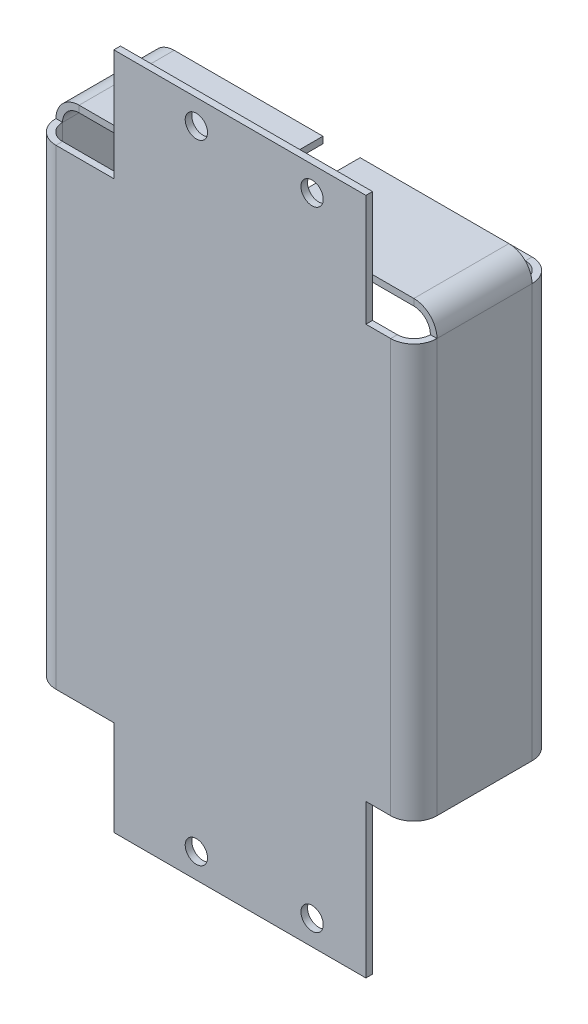
SolidWorks part; units mm, degrees
note: The reader was unsure of these and kept them because the rebuilt part matched: flange length of "Edge-Flange1", "Edge-Flange4", "Edge-Flange5".
ref_plane "Front Plane" through (0, 0, 0) normal (0, 0, 1) x (1, 0, 0)
ref_plane "Top Plane" through (0, 0, 0) normal (0, 1, 0) x (1, 0, 0)
ref_plane "Right Plane" through (0, 0, 0) normal (1, 0, 0) x (0, 0, -1)
sketch "Sketch1" plane through (0, 0, 0) normal (0, 0, 1) x (1, 0, 0)
  line L0 (16.25, 0) -> (16.25, -18.5)
  line L1 (21.25, 50) -> (16.25, 50)
  line L2 (21.25, 50) -> (21.25, 0)
  line L3 (21.25, 0) -> (16.25, 0)
  line L4 (-23.25, 50) -> (-23.25, -7)
  line L5 (16.25, -18.5) -> (-14.25, -18.5)
  line L6 (-14.25, -18.5) -> (-14.25, -7)
  line L7 (16.25, 50) -> (16.25, 63.5)
  line L9 (16.25, 63.5) -> (-14.25, 63.5)
  line L10 (-14.25, 63.5) -> (-14.25, 50)
  line L11 (-14.25, -7) -> (-23.25, -7)
  line L12 (-14.25, 50) -> (-23.25, 50)
  circle A0 centre (9.7378, -15.5) radius 1.35
  circle A1 centre (-4.2622, -15.5) radius 1.35
  circle A2 centre (9.7378, 60.5) radius 1.35
  circle A3 centre (-4.2622, 60.5) radius 1.35
  dimension "D6" = 6.5122
  dimension "D7" = 3
  dimension "D8" = 2.7
  dimension "D9" = 3
  dimension "D10" = 14
  dimension "D11" = 76
  dimension "D12" = 14
  dimension "D13" = 3
  dimension "D14" = 3
  dimension "D1" = 50
  dimension "D2" = 9
  dimension "D3" = 82
  dimension "D4" = 13.5
  dimension "D5" = 30.5
  dimension "D15" = 11.5
  dimension "D16" = 5
sheet metal parameters "Sheet-Metal1" thickness 0.8 parameters "D1"=2
base flange "Base-Flange1" sketch "Sketch1" thickness 0.8 reverse thickness direction yes parameters "D1"=2
edge flange "Edge-Flange1" sketch "Sketch6" flange profiles "Sketch6", "Sketch11" flange angle 90 flange length 13.5 flange position material outside bend radius 2 thickness 0.8 parameters "D6"=10, "D8"=1
sketch "Sketch6" plane through (21.25, 0, 0) normal (-1, 0, 0) x (0, 1, 0)
  line L2 (0, 0) -> (0, 13.5)
  line L3 (0, 13.5) -> (50, 13.5)
  line L4 (50, 13.5) -> (50, 0)
  line L6 (50, 0) -> (0, 0) construction
  line L7 (50, 0) -> (0, 0)
sketch "Sketch11" plane through (-23.25, 0, 0) normal (1, 0, 0) x (0, -1, 0)
  line L0 (7, 0) -> (-50, 0) construction
  line L1 (7, 0) -> (-50, 0)
  line L2 (7, 0) -> (7, 13.5)
  line L3 (7, 13.5) -> (-50, 13.5)
  line L4 (-50, 13.5) -> (-50, 0)
bend "EdgeBend1" bend radius 2 bend angle 90 parameters "D5"=1
bend "EdgeBend3" bend radius 2 bend angle 90 parameters "D5"=2
edge flange "Edge-Flange4" sketch "Sketch19" flange profiles "Sketch19", "Sketch20" flange angle 90 flange length 20 flange position bend outside bend radius 2 thickness 0.8 parameters "D6"=10, "D8"=1
sketch "Sketch19" plane through (21.25, 50, 0) normal (0, -1, 0) x (0, 0, 1)
  line L2 (-13.5, 0) -> (-13.5, 20)
  line L3 (-13.5, 20) -> (-2, 20)
  line L4 (-2, 20) -> (-2, 0)
  line L6 (-2, 0) -> (-13.5, 0) construction
  line L7 (-2, 0) -> (-13.5, 0)
sketch "Sketch20" plane through (-23.25, 50, 0) normal (0, -1, 0) x (0, 0, -1)
  line L0 (13.5, 0) -> (2, 0) construction
  line L1 (13.5, 0) -> (2, 0)
  line L2 (13.5, 0) -> (13.5, 20)
  line L3 (13.5, 20) -> (2, 20)
  line L4 (2, 20) -> (2, 0)
bend "EdgeBend5" bend radius 2 bend angle 90 parameters "D5"=3
bend "EdgeBend6" bend radius 2 bend angle 90 parameters "D5"=4
edge flange "Edge-Flange5" sketch "Sketch28" flange profiles "Sketch28", "Sketch29" flange angle 90 flange length 10 flange position bend outside bend radius 2 thickness 0.8 parameters "D6"=10, "D8"=1
sketch "Sketch28" plane through (21.25, 0, -13.5) normal (0, 0, 1) x (0, 1, 0)
  line L1 (50, 0) -> (0, 0) construction
  line L2 (0, 0) -> (0, 10)
  line L3 (0, 10) -> (50, 10)
  line L4 (50, 10) -> (50, 0)
  line L5 (50, 0) -> (0, 0)
sketch "Sketch29" plane through (-23.25, 0, -13.5) normal (0, 0, 1) x (0, -1, 0)
  line L0 (7, 0) -> (-50, 0) construction
  line L1 (7, 0) -> (-50, 0)
  line L2 (7, 0) -> (7, 10)
  line L3 (7, 10) -> (-50, 10)
  line L4 (-50, 10) -> (-50, 0)
bend "EdgeBend7" bend radius 2 bend angle 90 parameters "D5"=5
bend "EdgeBend8" bend radius 2 bend angle 90 parameters "D5"=6
flat pattern "Flat-Pattern1" [suppressed]
sketch "Bend-Lines1" plane through (0, 0, 0.8) normal (0, 0, 1) x (1, 0, 0)
  line L0 (-38.3766, -7) -> (-38.3766, 50) construction
  line L1 (36.3766, 50) -> (36.3766, 0) construction
  line L2 (-36.5011, 51.8755) -> (-25.0011, 51.8755) construction
  line L3 (23.0011, 51.8755) -> (34.5011, 51.8755) construction
  line L4 (-23.1255, -7) -> (-23.1255, 50) construction
  line L5 (21.1255, 50) -> (21.1255, 0) construction
  line L6 (-38.3766, -7) -> (-38.3766, 50) construction
  line L7 (36.3766, 50) -> (36.3766, 0) construction
  line L8 (-36.5011, 51.8755) -> (-25.0011, 51.8755) construction
  line L9 (23.0011, 51.8755) -> (34.5011, 51.8755) construction
  line L10 (-23.1255, -7) -> (-23.1255, 50) construction
  line L11 (21.1255, 50) -> (21.1255, 0) construction
sketch3d "Bounding-Box1" [suppressed]
  line L0 (-69.5021, -18.5, 0) -> (25.0021, -18.5, 0) construction
  line L1 (-69.5021, 71.7511, 0) -> (25.0021, 71.7511, 0) construction
  line L2 (-69.5021, -18.5, 0) -> (-69.5021, 71.7511, 0) construction
  line L3 (25.0021, -18.5, 0) -> (25.0021, 71.7511, 0) construction
bend of the flat pattern "Flatten-<EdgeBend1>1"
bend of the flat pattern "Flatten-<EdgeBend3>1"
bend of the flat pattern "Flatten-<EdgeBend5>1"
bend of the flat pattern "Flatten-<EdgeBend6>1"
bend of the flat pattern "Flatten-<EdgeBend7>1"
bend of the flat pattern "Flatten-<EdgeBend8>1"
fillet "Fillet1" [suppressed] radius 2
fillet "Fillet2" [suppressed] radius 1.88
